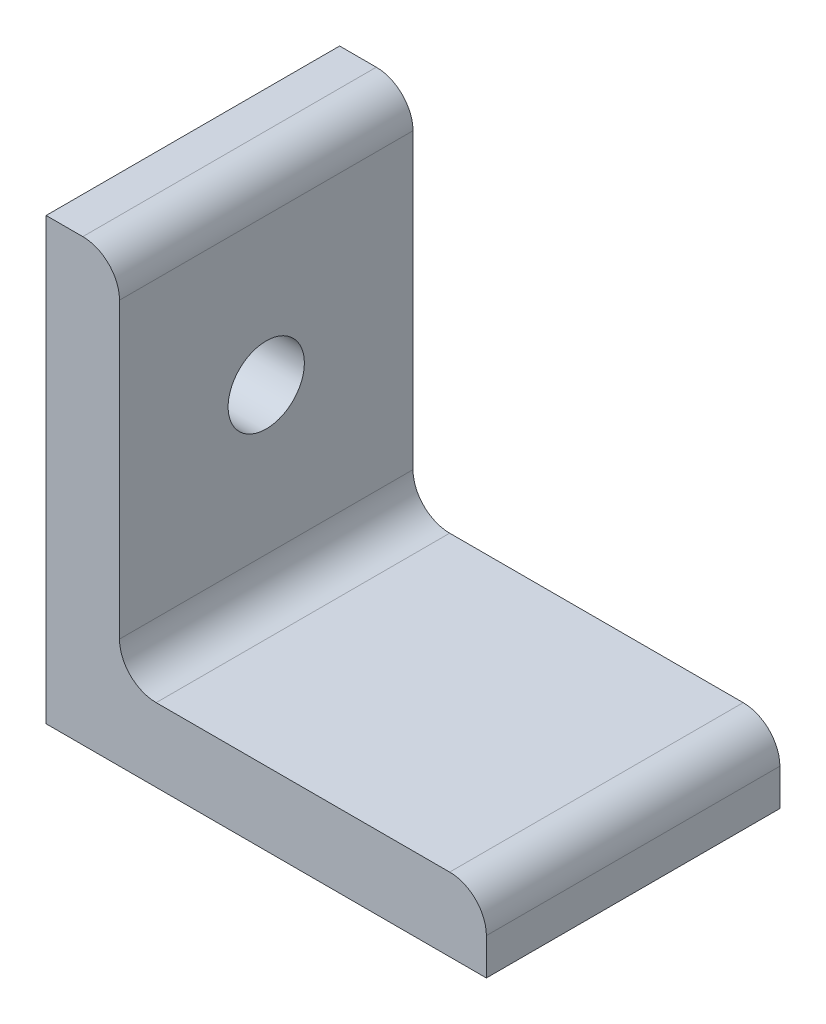
SolidWorks part; units mm, degrees
material "AISI 316 Stainless Steel Sheet (SS)"
ref_plane "Front Plane" through (0, 0, 0) normal (0, 0, 1) x (1, 0, 0)
ref_plane "Top Plane" through (0, 0, 0) normal (0, 1, 0) x (1, 0, 0)
ref_plane "Right Plane" through (0, 0, 0) normal (1, 0, 0) x (0, 0, -1)
sketch "Sketch1" plane through (0, 0, 0) normal (0, 0, 1) x (1, 0, 0)
  line L0 (0, 19.05) -> (0, 0) construction
  line L1 (0, 0) -> (19.05, 0) construction
  line L2 (19.05, 0) -> (19.05, 3.175) construction
  line L3 (19.05, 3.175) -> (3.175, 3.175) construction
  line L4 (3.175, 3.175) -> (3.175, 19.05) construction
  line L6 (3.175, 19.05) -> (0, 19.05) construction
  point P4 (0, 0)
  dimension "Outside Height" = 19.05
  dimension "Outside Width" = 19.05
  dimension "Wall Thickness" = 3.175
  dimension "Inside Width" = 15.875
  dimension "Inside Height" = 15.875
sketch "Sketch2" plane through (0, 0, 0) normal (1, 0, 0) x (0, 0, -1)
  line L0 (76.2, 0) -> (-76.2, 0) construction
  line L1 (-76.2, 12.7) -> (-76.2, -12.7) construction
  line L2 (76.2, 12.7) -> (76.2, -12.7) construction
  point P0 (-54.2925, 0)
  point P4 (0, 0)
  point P6 (54.2925, 0)
  point P10 (76.2, 0)
  point P12 (-76.2, 0)
  dimension "Length" = 152.4
  dimension "D1" = 21.9075
  dimension "D2" = 21.9075
  dimension "D3" = 25.4
sketch "Sketch3" plane through (0, 0, 0) normal (0, 0, 1) x (1, 0, 0)
  line L0 (3.175, 19.05) -> (0, 19.05)
  line L1 (0, 19.05) -> (0, 0)
  line L2 (0, 0) -> (19.05, 0)
  line L3 (19.05, 0) -> (19.05, 3.175)
  line L4 (19.05, 3.175) -> (3.175, 3.175)
  line L5 (3.175, 3.175) -> (3.175, 19.05)
extrude "Boss-Extrude1" add sketch "Sketch3" along normal mid plane 12.7
fillet "Fillet1" radius 1.5875 3 edges at (19.05, 3.175, 0) (3.175, 3.175, 0) (3.175, 19.05, 0)
sketch "Sketch4" plane through (3.175, 0, 0) normal (1, 0, 0) x (0, 0, -1)
  line L2 (-6.35, 4.7625) -> (-6.35, 17.4625) construction
  line L3 (6.35, 17.4625) -> (-6.35, 17.4625) construction
  point P1 (0, 11.1125)
  dimension "D1" = 6.35
  dimension "D2" = 6.35
hole_wizard "M4x0.7 Tapped Hole1" positions "Sketch5" profile "Sketch6" tap size "M4x0.7" standard "ANSI Metric" end condition through all
sketch "Sketch5" plane through (3.175, 0, 0) normal (1, 0, 0) x (0, 0, -1)
  point P0 (0, 11.1125)
sketch "Sketch6" plane through (3.175, 11.1125, 0) normal (0, 1, 0) x (0, 0, -1)
  line L0 (0, 0) -> (0, 3.175)
  line L1 (0, 3.175) -> (1.65, 3.175)
  line L2 (1.65, 3.175) -> (1.65, 0)
  line L5 (1.65, 0) -> (0, 0)
  line L11 (0, -6.35) -> (0, 107.95) construction
  dimension "Thru Tap Drill Dia." = 3.3
  dimension "Thru Tap Drill Depth" = 3.175
equation "\"D1@Boss-Extrude1\"=\"Length@Sketch2\""
equation "\"D1@Sketch2\" = \"Outside Width@Sketch1\" * 1.15"
equation "\"D2@Sketch2\"=\"D1@Sketch2\""
equation "\"D1@Fillet1\"=\"Wall Thickness@Sketch1\"/2"
